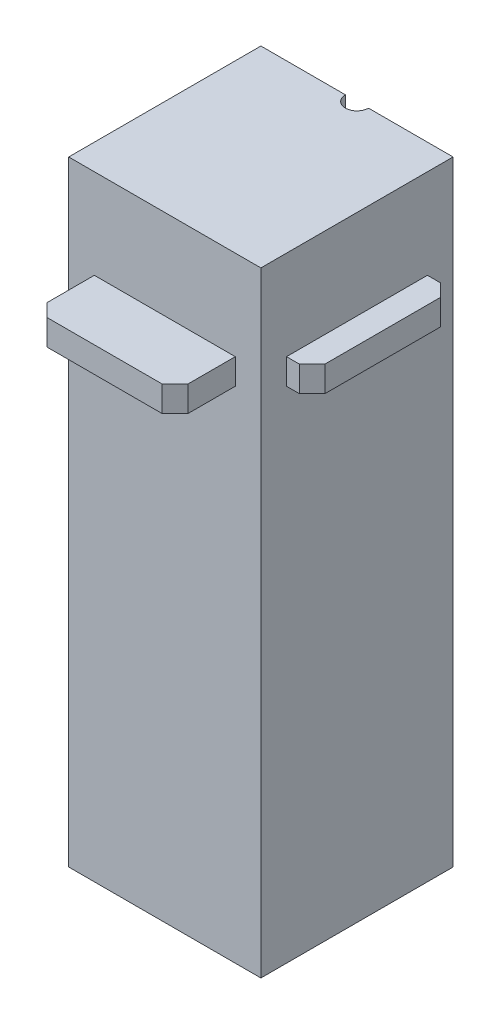
SolidWorks part; units mm, degrees
ref_plane "Front Plane" through (0, 0, 0) normal (0, 0, 1) x (1, 0, 0)
ref_plane "Top Plane" through (0, 0, 0) normal (0, 1, 0) x (1, 0, 0)
ref_plane "Right Plane" through (0, 0, 0) normal (1, 0, 0) x (0, 0, -1)
sketch "Sketch2" plane through (0, 0, 0) normal (0, 1, 0) x (1, 0, 0)
  line L1 (75, -75) -> (-75, -75)
  line L2 (75, -75) -> (75, 75)
  line L3 (75, 75) -> (-75, 75)
  line L4 (-75, -75) -> (-75, 75)
  line L5 (75, -75) -> (-75, 75) construction
  line L6 (75, 75) -> (-75, -75) construction
  line L7 (65, -65) -> (-65, -65)
  line L8 (65, -65) -> (65, 65)
  line L9 (65, 65) -> (-65, 65)
  line L10 (-65, -65) -> (-65, 65)
  line L11 (65, -65) -> (-65, 65) construction
  line L12 (65, 65) -> (-65, -65) construction
  point P0 (0, 0)
  point P6 (0, 0)
  dimension "D1" = 150
  dimension "D2" = 150
  dimension "D3" = 10
extrude "Boss-Extrude2" add sketch "Sketch2" along normal blind 450
sketch "Sketch4" plane through (0, 450, 0) normal (0, 1, 0) x (1, 0, 0)
  line L1 (75, -75) -> (-75, -75)
  line L2 (75, -75) -> (75, 75)
  line L3 (75, 75) -> (-75, 75)
  line L4 (-75, -75) -> (-75, 75)
  line L5 (75, -75) -> (-75, 75) construction
  line L6 (75, 75) -> (-75, -75) construction
  point P0 (0, 0)
extrude "Boss-Extrude3" add sketch "Sketch4" along normal blind 15
extrude "Boss-Extrude4" add sketch "Sketch4<2>" against normal blind 15 from offset 450 offset against normal yes
sketch "Sketch4<2>" plane through (0, 450, 0) normal (0, 1, 0) x (1, 0, 0) same geometry as "Sketch4"
sketch "Sketch5" plane through (0, -15, 0) normal (0, -1, 0) x (1, 0, 0)
  line L0 (-75, -75) -> (-75, 75) construction
  circle A0 centre (-35, 0) radius 30
  dimension "D1" = 40
extrude "Cut-Extrude1" cut sketch "Sketch5" against normal blind 15
sketch "Sketch7" plane through (0, 450, 0) normal (0, -1, 0) x (1, 0, 0)
  line L1 (10, -20) -> (-10, -20)
  line L2 (10, -20) -> (10, -10)
  line L3 (10, -10) -> (-10, -10)
  line L4 (-10, -20) -> (-10, -10)
  line L5 (10, -20) -> (-10, -10) construction
  line L6 (10, -10) -> (-10, -20) construction
  point P0 (0, -15)
  dimension "D1" = 10
  dimension "D2" = 10
  dimension "D3" = 20
extrude "Boss-Extrude5" add sketch "Sketch7" along normal blind 50
mirror "Mirror1" about plane through (0, 0, 0) normal (0, 0, 1) of "Boss-Extrude5"
sketch "Sketch9" plane through (0, 0, 0) normal (0, 0, 1) x (1, 0, 0)
  line L1 (10, 450) -> (-10, 450) construction
  circle A0 centre (0, 420) radius 25
  dimension "D1" = 30
extrude "Boss-Extrude6" add sketch "Sketch9" along normal blind 20 from offset 10 offset against normal yes
sketch "Sketch10" plane through (0, 0, -10) normal (0, 0, 1) x (1, 0, 0)
  line L1 (10, 450) -> (-10, 450) construction
  circle A0 centre (0, 420) radius 22
  circle A1 centre (0, 420) radius 25
  dimension "D1" = 30
extrude "Cut-Extrude3" cut sketch "Sketch10" along normal blind 10 from offset 5
sketch "Sketch12" plane through (0, 0, 0) normal (0, 1, 0) x (1, 0, 0)
  line L0 (65, 65) -> (-65, 65) construction
  line L1 (45, 23) -> (25, 23)
  line L2 (45, 23) -> (45, 63)
  line L3 (45, 63) -> (25, 63)
  line L4 (25, 23) -> (25, 63)
  line L5 (45, 23) -> (25, 63) construction
  line L6 (45, 63) -> (25, 23) construction
  line L7 (65, -65) -> (65, 65) construction
  point P0 (35, 43)
  dimension "D1" = 20
  dimension "D2" = 40
  dimension "D3" = 2
  dimension "D4" = 30
extrude "Boss-Extrude7" add sketch "Sketch12" along normal blind 25
sketch "Sketch13" plane through (0, 0, -23) normal (0, 0, 1) x (1, 0, 0)
  circle A0 centre (35.1215, 12.6107) radius 4
extrude "Boss-Extrude8" add sketch "Sketch13" along normal blind 23
sketch "Sketch14" plane through (0, 465, 0) normal (0, 1, 0) x (1, 0, 0)
  line L0 (75, 75) -> (-75, 75) construction
  circle A0 centre (0, 75) radius 9
extrude "Cut-Extrude5" cut sketch "Sketch14" against normal blind 500
sketch "Sketch17" plane through (0, 465, 0) normal (0, 1, 0) x (1, 0, 0)
  line L0 (-9, 75) -> (-13, 75)
  line L1 (9, 75) -> (13, 75)
  line L2 (75, -75) -> (75, 75) construction
  arc A0 (13, 75) -> (-13, 75) centre (0, 75) ccw
  arc A1 (9, 75) -> (-9, 75) centre (0, 75) ccw
  dimension "D1" = 75
extrude "Boss-Extrude10" add sketch "Sketch17" against normal blind 200 from offset 150 offset against normal yes
sketch "Sketch18" plane through (75, 0, 0) normal (1, 0, 0) x (0, 0, -1)
  line L0 (-55, 395) -> (55, 395)
  line L1 (55, 395) -> (55, 375)
  line L2 (55, 375) -> (-55, 375)
  line L3 (-55, 375) -> (-55, 395)
  line L4 (-75, 465) -> (75, 465) construction
  point P6 (0, 395)
  point P7 (0, 465)
  dimension "D1" = 70
  dimension "D2" = 20
  dimension "D3" = 110
extrude "Boss-Extrude11" add sketch "Sketch18" along normal blind 20
chamfer "Chamfer1" distance 10 angle 45 1 edges at (95, 385, 55)
chamfer "Chamfer2" distance 10 angle 45 1 edges at (95, 385, -55)
sketch "Sketch19" plane through (0, 0, 75) normal (0, 0, 1) x (1, 0, 0)
  line L0 (-55, 395) -> (55, 395)
  line L1 (55, 395) -> (55, 375)
  line L2 (55, 375) -> (-55, 375)
  line L3 (-55, 375) -> (-55, 395)
  line L4 (-75, 465) -> (75, 465) construction
  point P6 (0, 465)
  point P7 (0, 375)
  dimension "D1" = 70
  dimension "D2" = 110
  dimension "D3" = 20
extrude "Boss-Extrude12" add sketch "Sketch19" along normal blind 47
chamfer "Chamfer3" distance 10 angle 45 2 edges at (-55, 385, 122) (55, 385, 122)
